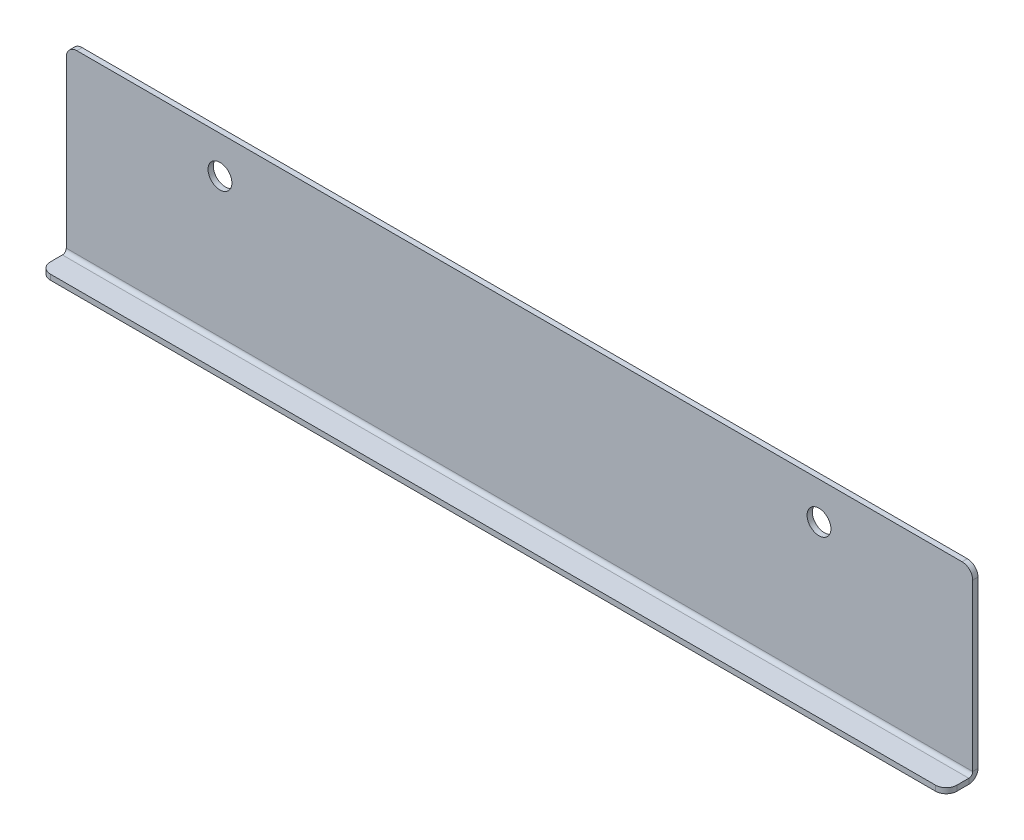
SolidWorks part; units mm, degrees
ref_plane "Plan de face" through (0, 0, 0) normal (0, 0, 1) x (1, 0, 0)
ref_plane "Plan de dessus" through (0, 0, 0) normal (0, 1, 0) x (1, 0, 0)
ref_plane "Plan de droite" through (0, 0, 0) normal (1, 0, 0) x (0, 0, -1)
sketch "Esquisse1" plane through (0, 0, 0) normal (0, 0, 1) x (1, 0, 0)
  line L0 (0.55, 0) -> (-0.55, 0) construction
  line L1 (-85.5, -20) -> (85.5, -20)
  line L2 (-85.5, -20) -> (-85.5, 14)
  line L3 (-85.5, 14) -> (85.5, 14)
  line L4 (85.5, -20) -> (85.5, 14)
  line L5 (-85.5, -20) -> (85.5, 14) construction
  line L6 (-85.5, 14) -> (85.5, -20) construction
  line L7 (-56.5, 0) -> (-56.5, 14) construction
  line L8 (0, -0.55) -> (0, 0.55) construction
  circle A0 centre (-56.5, 7) radius 2.25
  circle A1 centre (56.5, 7) radius 2.25
  point P0 (0, -3)
  point P8 (85.5, -3)
  dimension "D4" = 4.5
  dimension "D1" = 171
  dimension "D2" = 20
  dimension "D3" = 17
  dimension "D5" = 29
base flange "Tôle de base pliée1" sketch "Esquisse1" thickness 1 reverse thickness direction no parameters "D1"=0.7366
edge flange "Tôle pliée sur arête1" sketch "Esquisse4" flange angle 90 flange length 5 flange position material outside bend radius 0.7366 thickness 1 relief rectangular parameters "D6"=10
sketch "Esquisse4" plane through (0, -20, 0) normal (0, -1, 0) x (1, 0, 0)
  line L0 (-85.5, 0) -> (85.5, 0) construction
  line L1 (-85.5, 0) -> (85.5, 0)
  line L2 (-85.5, 0) -> (-85.5, 5)
  line L3 (-85.5, 5) -> (85.5, 5)
  line L4 (85.5, 5) -> (85.5, 0)
bend "Pli d'arête1" bend radius 0.7366 bend angle 90 parameters "D5"=1
fillet "Congé1" radius 2 4 edges at (-85.5, 14, -0.5) (85.5, 14, -0.5) (85.5, -20.5, 5) (-85.5, -20.5, 5)
